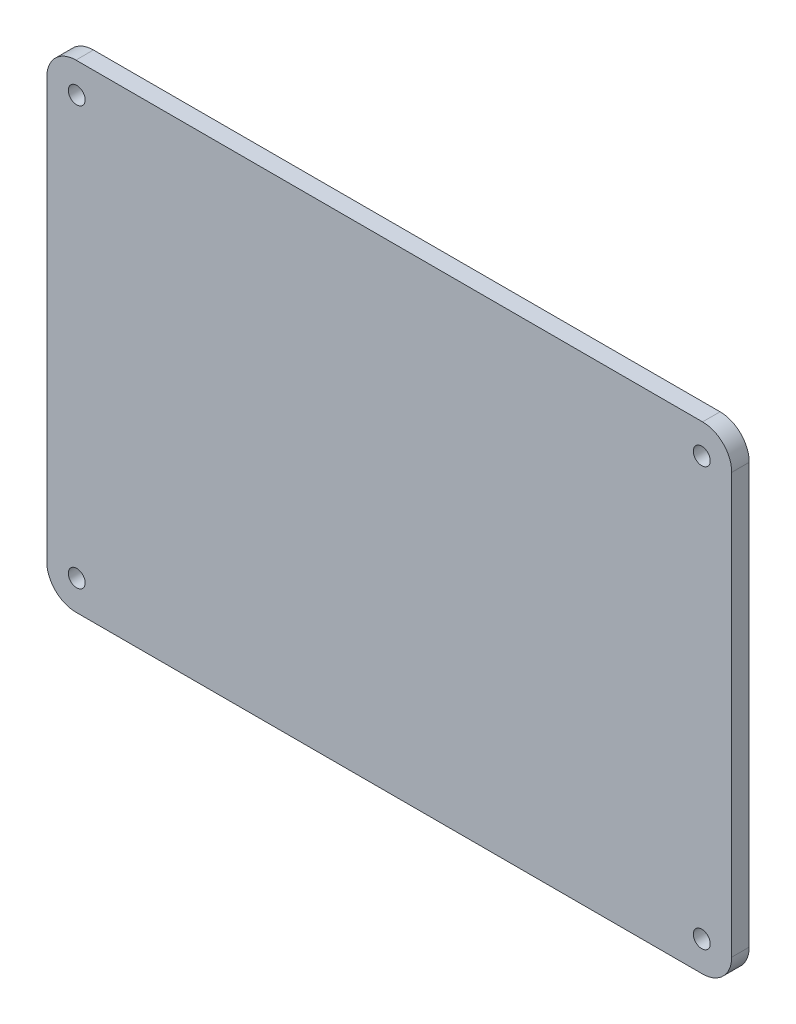
SolidWorks part; units mm, degrees
ref_plane "Front Plane" through (0, 0, 0) normal (0, 0, 1) x (1, 0, 0)
ref_plane "Top Plane" through (0, 0, 0) normal (0, 1, 0) x (1, 0, 0)
ref_plane "Right Plane" through (0, 0, 0) normal (1, 0, 0) x (0, 0, -1)
sketch "Sketch1" plane through (0, 0, 0) normal (0, 0, 1) x (1, 0, 0)
  line L0 (-700.5296, 908.6614) -> (-593.0698, 908.6614)
  line L1 (-588.0698, 903.6614) -> (-588.0698, 831.66)
  line L2 (-700.5296, 826.66) -> (-593.0698, 826.66)
  line L3 (-705.5296, 831.66) -> (-705.5296, 903.6614)
  arc A0 (-700.5296, 908.6614) -> (-705.5296, 903.6614) centre (-700.5296, 903.6614) ccw
  arc A1 (-593.0698, 908.6614) -> (-588.0698, 903.6614) centre (-593.0698, 903.6614) cw
  arc A2 (-588.0698, 831.66) -> (-593.0698, 826.66) centre (-593.0698, 831.66) cw
  arc A3 (-705.5296, 831.66) -> (-700.5296, 826.66) centre (-700.5296, 831.66) ccw
extrude "Boss-Extrude1" add sketch "Sketch1" along normal blind 3
sketch "Sketch2" plane through (0, 0, 3) normal (0, 0, 1) x (1, 0, 0)
  point P0 (-700.3935, 903.5254)
  point P1 (-593.2058, 903.5254)
  point P3 (-593.2058, 831.796)
  point P5 (-700.3935, 831.796)
hole_wizard "M2.5 Clearance Hole1" positions "Sketch2" profile "Sketch3" hole size "M2.5" standard "ANSI Metric" end condition up to next
sketch "Sketch3" plane through (-700.3935, 903.5254, 3) normal (1, 0, 0) x (0, -1, 0)
  line L0 (0, 0) -> (0, 3)
  line L1 (0, 3) -> (1.45, 3)
  line L2 (1.45, 3) -> (1.45, 0)
  line L5 (1.45, 0) -> (0, 0)
  line L11 (0, -6.35) -> (0, 107.95) construction
  dimension "Thru Hole Dia." = 2.9
  dimension "Thru Hole Depth" = 3
